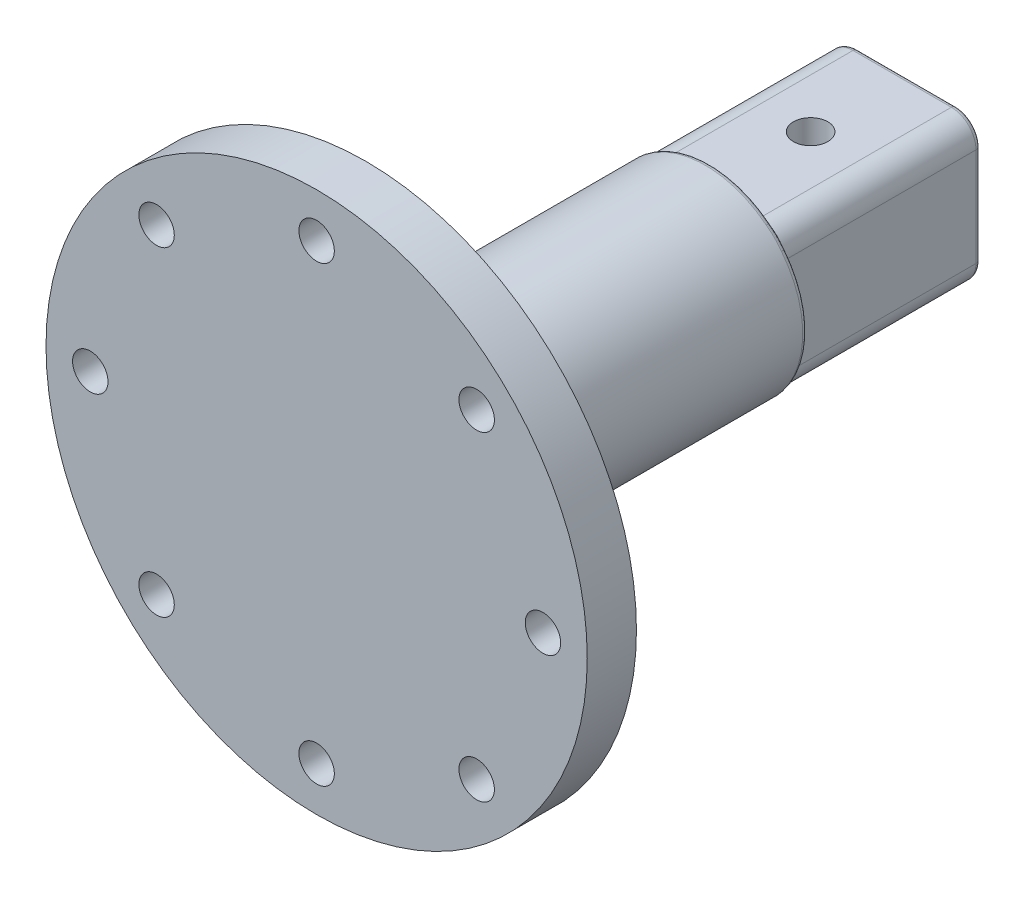
SolidWorks part; units mm, degrees
ref_plane "Front Plane" through (0, 0, 0) normal (0, 0, 1) x (1, 0, 0)
ref_plane "Top Plane" through (0, 0, 0) normal (0, 1, 0) x (1, 0, 0)
ref_plane "Right Plane" through (0, 0, 0) normal (1, 0, 0) x (0, 0, -1)
sketch "Sketch1" [suppressed] plane through (0, 0, 0) normal (0, 0, 1) x (1, 0, 0)
  circle A0 centre (0, 0) radius 2.05
  circle A1 centre (0, 0) radius 7.5
  dimension "D1" = 4.1
  dimension "D2" = 15
sketch "Sketch2" [suppressed] plane through (0, 0, 0) normal (0, 0, 1) x (1, 0, 0)
  circle A0 centre (0, 0) radius 7.5
  circle A1 centre (0, 0) radius 5
  dimension "D1" = 10
  dimension "D2" = 15
sketch "Sketch5" plane through (0, 0, 0) normal (0, 0, 1) x (1, 0, 0)
  circle A0 centre (0, 0) radius 9.9
  dimension "D1" = 19.8
extrude "Boss-Extrude1" add sketch "Sketch5" along normal blind 35
sketch "Sketch10" plane through (0, 0, 35) normal (0, 0, 1) x (1, 0, 0)
  circle A1 centre (0, 0) radius 27.5
  circle A2 centre (0, 23) radius 1.8
  circle A3 centre (16.2635, 16.2635) radius 1.8
  circle A4 centre (23, 0) radius 1.8
  circle A5 centre (16.2635, -16.2635) radius 1.8
  circle A6 centre (0, -23) radius 1.8
  circle A7 centre (-16.2635, -16.2635) radius 1.8
  circle A8 centre (-23, 0) radius 1.8
  circle A9 centre (-16.2635, 16.2635) radius 1.8
  point P22 (0, 0)
  dimension "D2" = 55
  dimension "D3" = 3.6
  dimension "D4" = 23
  dimension "D5" = 8
extrude "Boss-Extrude2" add sketch "Sketch10" along normal blind 5
sketch "Sketch13" plane through (0, 0, 40) normal (0, 0, 1) x (1, 0, 0)
  circle A0 centre (0, 0) radius 7.5
  dimension "D1" = 15
extrude "Cut-Extrude2" [suppressed] cut sketch "Sketch13" against normal blind 3
sketch "Sketch11" plane through (0, 0, 0) normal (0, 0, -1) x (-1, 0, 0)
  line L9 (-5, 7.5) -> (5, 7.5)
  line L10 (-7.5, 5) -> (-7.5, -5)
  line L11 (-5, -7.5) -> (5, -7.5)
  line L12 (7.5, 5) -> (7.5, -5)
  line L13 (-7.5, 7.5) -> (7.5, -7.5) construction
  line L14 (-7.5, -7.5) -> (7.5, 7.5) construction
  arc A0 (7.5, 5) -> (5, 7.5) centre (5, 5) ccw
  arc A1 (5, -7.5) -> (7.5, -5) centre (5, -5) ccw
  arc A2 (-7.5, -5) -> (-5, -7.5) centre (-5, -5) ccw
  arc A3 (-5, 7.5) -> (-7.5, 5) centre (-5, 5) ccw
  point P0 (0, 0)
  dimension "D3" = 2.5
  dimension "D4" = 2.5
  dimension "D1" = 15
  dimension "D2" = 15
extrude "Boss-Extrude3" add sketch "Sketch11" along normal blind 20
sketch "Sketch14" plane through (0, 0, 0) normal (0, 1, 0) x (1, 0, 0)
  line L0 (-5, 20) -> (5, 20) construction
  circle A0 centre (0, 10.2) radius 1.75
  dimension "D2" = 3.5
  dimension "D1" = 9.8
extrude "Cut-Extrude4" cut sketch "Sketch14" against normal through all both and the other way through all
fillet "Fillet1" radius 0.5 1 edges at (9.9, 0, 0)
fillet "Fillet2" radius 0.5 8 edges at (-7.5, 0, -20) (-6.7678, -6.7678, -20) (0, -7.5, -20) (6.7678, -6.7678, -20) (7.5, 0, -20) (6.7678, 6.7678, -20) (0, 7.5, -20) (-6.7678, 6.7678, -20)
fillet "Fillet3" radius 0.5 1 edges at (9.9, 0, 35)
